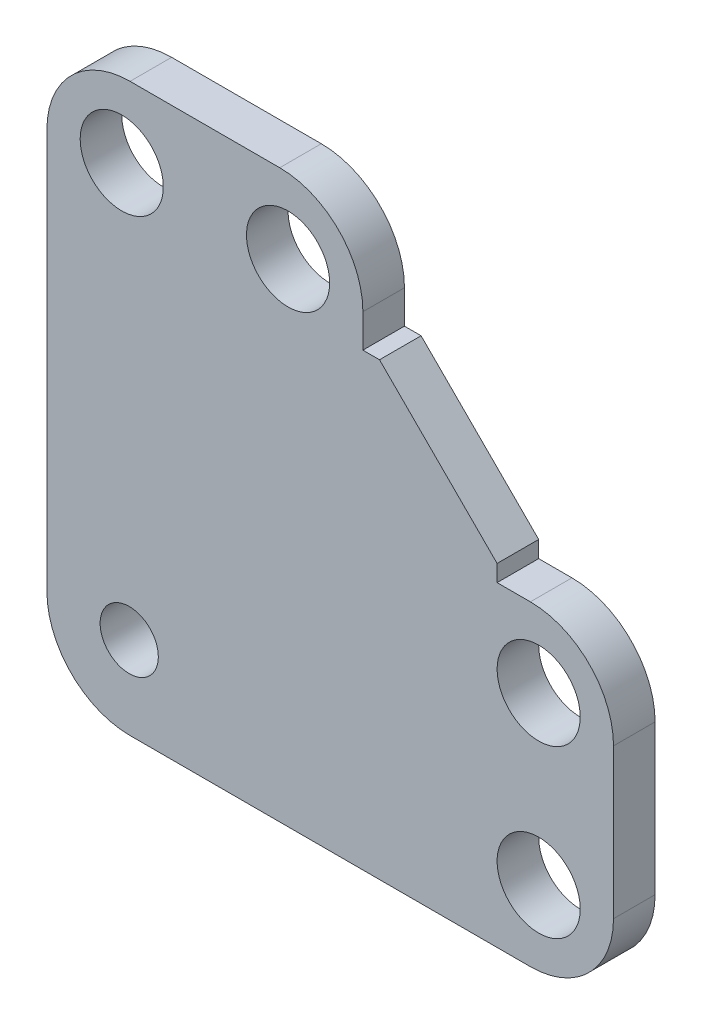
SolidWorks part; units mm, degrees
ref_plane "Plan de face" through (0, 0, 0) normal (0, 0, 1) x (1, 0, 0)
ref_plane "Plan de dessus" through (0, 0, 0) normal (0, 1, 0) x (1, 0, 0)
ref_plane "Plan de droite" through (0, 0, 0) normal (1, 0, 0) x (0, 0, -1)
sketch "Esquisse1" plane through (0, 0, 0) normal (0, 0, 1) x (1, 0, 0)
  line L0 (0, 0) -> (54.1421, 0)
  line L1 (54.1421, 0) -> (54.1421, 40)
  line L2 (54.1421, 40) -> (40, 54.1421)
  line L3 (40, 54.1421) -> (0, 54.1421)
  line L4 (0, 54.1421) -> (0, 0)
  dimension "D1" = 135
  dimension "D2" = 20
  dimension "D3" = 40
extrude "Boss.-Extru.1" add sketch "Esquisse1" along normal blind 5
sketch "Esquisse3" plane through (0, 0, 5) normal (0, 0, 1) x (1, 0, 0)
  line L0 (47.0711, 47.0711) -> (0, 0) construction
  line L1 (0, 54.1421) -> (38, 54.1421)
  line L2 (0, 54.1421) -> (0, 68.1421)
  line L3 (0, 68.1421) -> (38, 68.1421)
  line L4 (38, 54.1421) -> (38, 68.1421)
  line L5 (54.1421, 40) -> (40, 54.1421) construction
  line L6 (54.1421, 38) -> (68.1421, 38)
  line L7 (68.1421, 0) -> (68.1421, 38)
  line L8 (54.1421, 0) -> (68.1421, 0)
  line L9 (54.1421, 0) -> (54.1421, 38)
  dimension "D1" = 2
  dimension "D2" = 14
extrude "Boss.-Extru.2" add sketch "Esquisse3" against normal up to vertex (5 mm away) up to point (40, 54.1421, 0)
sketch "Esquisse4" plane through (0, 0, 5) normal (0, 0, 1) x (1, 0, 0)
  line L0 (38, 54.1421) -> (0, 54.1421) construction
  line L1 (0, 68.1421) -> (0, 0) construction
  line L2 (19, 54.1421) -> (19, 38.3704) construction
  line L3 (47.0711, 47.0711) -> (0, 0) construction
  line L4 (54.1421, 40) -> (40, 54.1421) construction
  line L5 (54.1421, 38) -> (54.1421, 0) construction
  circle A0 centre (29, 59.1421) radius 5
  circle A1 centre (9, 59.1421) radius 5
  circle A2 centre (59.1421, 9) radius 5
  circle A3 centre (59.1421, 29) radius 5
  circle A4 centre (9.8995, 9.8995) radius 3.5
  dimension "D1" = 20
  dimension "D2" = 10
  dimension "D3" = 14
  dimension "D4" = 7
extrude "Enlèv. mat.-Extru.2" cut sketch "Esquisse4" against normal through all
fillet "Congé1" radius 10 5 edges at (0, 0, 2.5) (68.1421, 0, 2.5) (68.1421, 38, 2.5) (0, 68.1421, 2.5) (38, 68.1421, 2.5)
